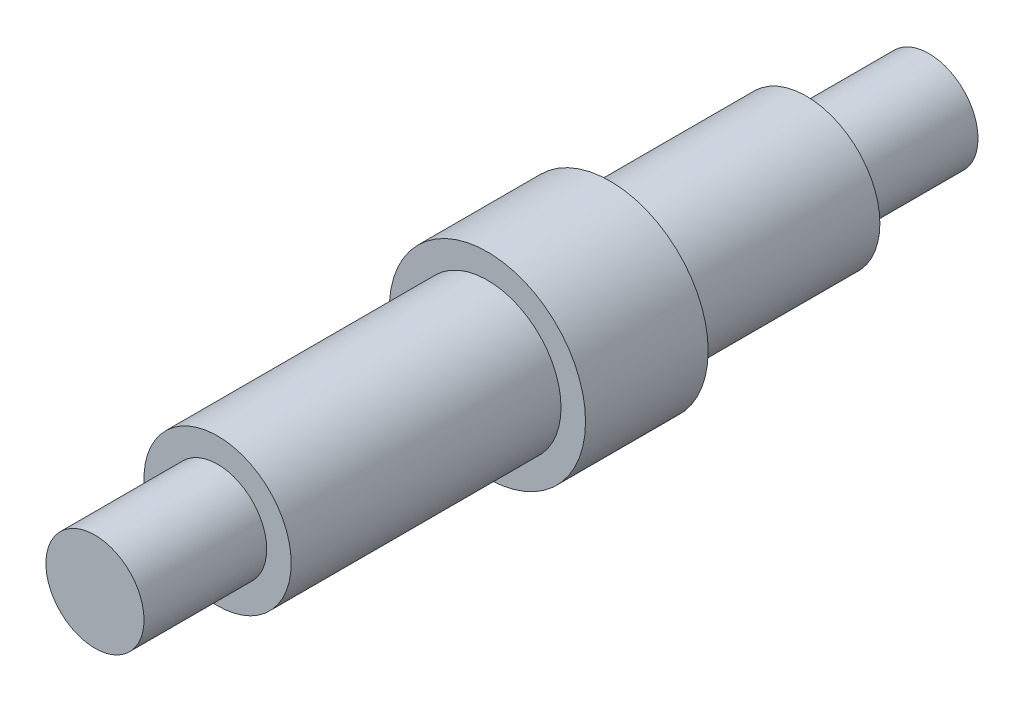
SolidWorks part; units mm, degrees
ref_plane "Front Plane" through (0, 0, 0) normal (0, 0, 1) x (1, 0, 0)
ref_plane "Top Plane" through (0, 0, 0) normal (0, 1, 0) x (1, 0, 0)
ref_plane "Right Plane" through (0, 0, 0) normal (1, 0, 0) x (0, 0, -1)
sketch "Sketch1" plane through (0, 0, 0) normal (0, 0, 1) x (1, 0, 0)
  circle A0 centre (0, 0) radius 2
  circle A1 centre (0, 0) radius 3
  circle A2 centre (0, 0) radius 4
extrude "Boss-Extrude1" add sketch "Sketch1" along normal blind 34 contours A0
extrude "Boss-Extrude2" add sketch "Sketch1<3>" along normal blind 24 from offset 5 contours A1
sketch "Sketch1<3>" plane through (0, 0, 0) normal (0, 0, 1) x (1, 0, 0) same geometry as "Sketch1"
extrude "Boss-Extrude3" add sketch "Sketch1<4>" along normal blind 5 from offset 13 contours A2
sketch "Sketch1<4>" plane through (0, 0, 0) normal (0, 0, 1) x (1, 0, 0) same geometry as "Sketch1"
